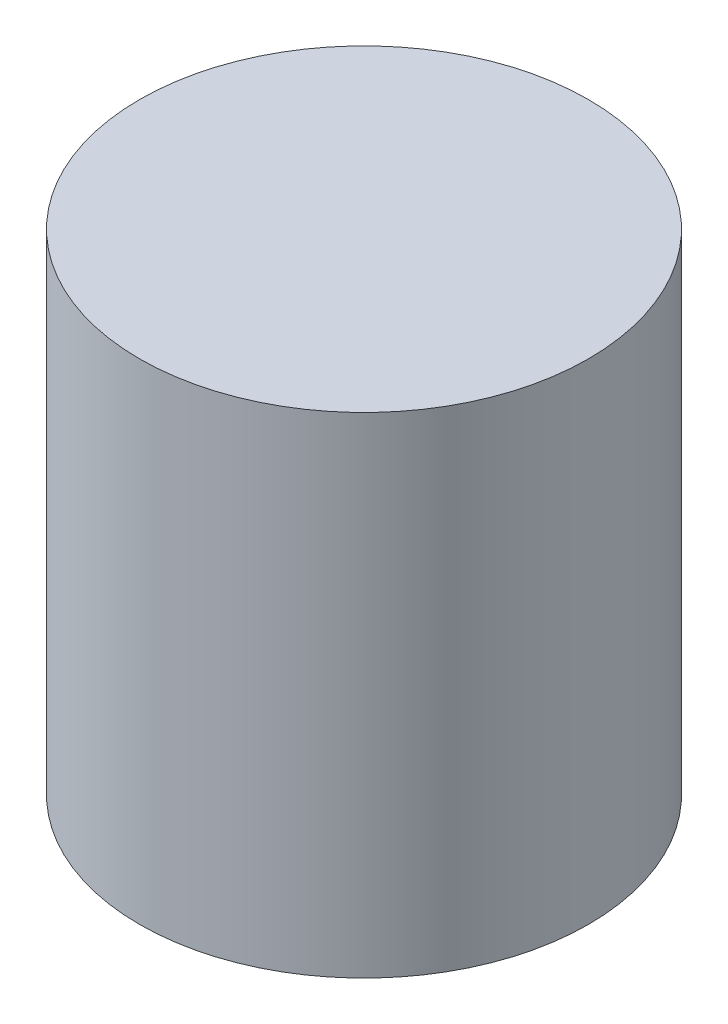
SolidWorks part; units mm, degrees
material "Silicon"
ref_plane "Front Plane" through (0, 0, 0) normal (0, 0, 1) x (1, 0, 0)
ref_plane "Top Plane" through (0, 0, 0) normal (0, 1, 0) x (1, 0, 0)
ref_plane "Right Plane" through (0, 0, 0) normal (1, 0, 0) x (0, 0, -1)
sketch "Sketch2" plane through (0, 0, 0) normal (0, 1, 0) x (1, 0, 0)
  circle A0 centre (0, 0) radius 69.85
  dimension "D1" = 139.7
extrude "Boss-Extrude1" add sketch "Sketch2" along normal blind 152.4
equation "\"PackedDiameter\"= 5.5"
equation "\"PackedLength\"= 6"
equation "\"D1@Sketch2\"=\"PackedDiameter\""
equation "\"D1@Boss-Extrude1\"=\"PackedLength\""
